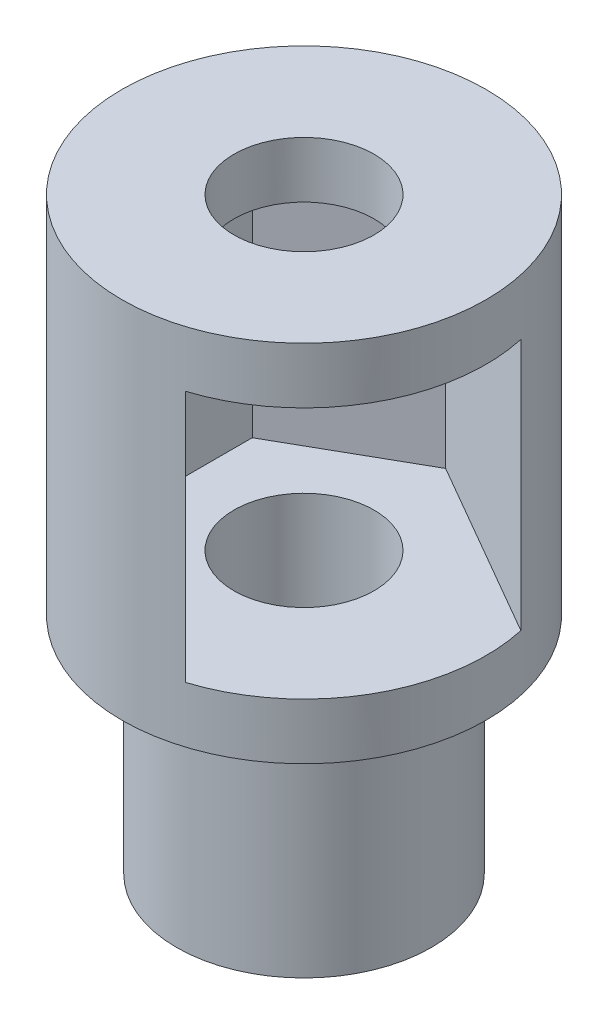
SolidWorks part; units mm, degrees
ref_plane "Front Plane" through (0, 0, 0) normal (0, 0, 1) x (1, 0, 0)
ref_plane "Top Plane" through (0, 0, 0) normal (0, 1, 0) x (1, 0, 0)
ref_plane "Right Plane" through (0, 0, 0) normal (1, 0, 0) x (0, 0, -1)
sketch "Sketch1" plane through (0, 0, 0) normal (0, 1, 0) x (1, 0, 0)
  circle A0 centre (0, 0) radius 4.55
  dimension "D1" = 9.1
extrude "Boss-Extrude1" add sketch "Sketch1" along normal blind 8 contours A0
sketch "Sketch2" plane through (0, 8, 0) normal (0, 1, 0) x (1, 0, 0)
  circle A0 centre (0, 0) radius 2.5
extrude "Cut-Extrude1" cut sketch "Sketch2" against normal blind 8
sketch "Sketch3" plane through (0, 8, 0) normal (0, 1, 0) x (1, 0, 0)
  circle A0 centre (0, 0) radius 6.5
  dimension "D1" = 13
extrude "Boss-Extrude4" add sketch "Sketch3" along normal blind 11 contours A0
sketch "Sketch5" plane through (0, 19, 0) normal (0, 1, 0) x (1, 0, 0)
  line L0 (0, 0) -> (4.3938, 0) construction
  line L3 (4.3938, 2.521) -> (4.3938, -2.521) construction
  line L5 (4.3938, -2.521) -> (-0.0062, -5.0614) construction
  line L9 (-0.0062, -5.0614) -> (-4.4062, -2.521) construction
  line L12 (-4.4062, -2.521) -> (-4.4062, 2.5597)
  line L13 (-4.4062, 2.5597) -> (-0.0062, 5.0614)
  line L14 (-0.0062, 5.0614) -> (4.3938, 2.521) construction
  line L15 (-4.1854, -2.6484) -> (43297.0847, -25002.6484) construction
  line L16 (0.0916, 5.0049) -> (43301.3618, -24994.9951) construction
  line L17 (7.8193, 0.5434) -> (3.436, -7.0487)
  line L18 (-0.0062, 5.0614) -> (7.8193, 0.5434)
  line L19 (3.436, -7.0487) -> (-4.4062, -2.521)
  circle A0 centre (0, 0) radius 6.5 construction
  point P6 (4.3938, 0)
  dimension "D1" = 120
extrude "Cut-Extrude2" cut sketch "Sketch5" against normal blind 9
sketch "Sketch6" plane through (0, 19, 0) normal (0, 1, 0) x (1, 0, 0)
  circle A0 centre (0, 0) radius 6.5
  dimension "D1" = 13
extrude "Boss-Extrude5" add sketch "Sketch6" along normal blind 2
sketch "Sketch7" plane through (0, 0, 0) normal (0, -1, 0) x (1, 0, 0)
  circle A0 centre (0, 0) radius 2.5
extrude "Cut-Extrude3" cut sketch "Sketch7" against normal through all
